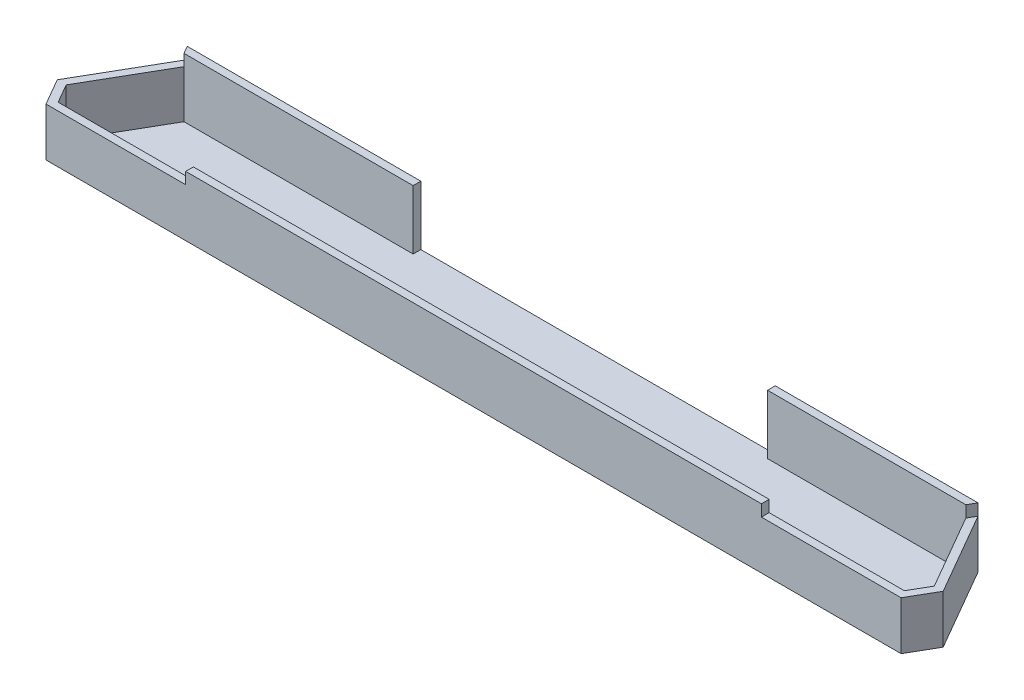
SolidWorks part; units mm, degrees
note: The reader was unsure of these and kept them because the rebuilt part matched: shared geometry of "Sketch1<3>", "Sketch1<4>".
ref_plane "Front Plane" through (0, 0, 0) normal (0, 0, 1) x (1, 0, 0)
ref_plane "Top Plane" through (0, 0, 0) normal (0, 1, 0) x (1, 0, 0)
ref_plane "Right Plane" through (0, 0, 0) normal (1, 0, 0) x (0, 0, -1)
sketch "Sketch1" plane through (0, 0, 0) normal (0, 1, 0) x (1, 0, 0)
  line L7 (-115, 0) -> (-111, -6.9282)
  line L9 (115, 0) -> (111, -6.9282)
  line L17 (-102.6494, 21.3918) -> (-101.4947, 19.3918)
  line L24 (102.6494, 21.3918) -> (101.4947, 19.3918)
  line L25 (-115, 0) -> (115, 0) construction
  line L26 (-115, 0) -> (-102.6494, 21.3918)
  line L27 (-113, -3.4641) -> (-107, 0) construction
  line L28 (0, -6.9282) -> (0, 21.3918) construction
  line L29 (113, -3.4641) -> (107, 0) construction
  line L30 (0, 21.3918) -> (-42.01, 21.3918) construction
  line L31 (-42.01, 21.3918) -> (-42.01, 19.3918)
  line L33 (-112.6906, 0) -> (-109.8453, -4.9282)
  line L36 (112.6906, 0) -> (109.8453, -4.9282)
  line L46 (-74.74, -4.9282) -> (74.74, -4.9282)
  line L49 (74.74, -6.9282) -> (-74.74, -6.9282)
  line L50 (-112.6906, 0) -> (-101.4947, 19.3918)
  line L51 (-102.6494, 21.3918) -> (-42.01, 21.3918)
  line L52 (-101.4947, 19.3918) -> (-42.01, 19.3918)
  line L53 (-42.01, 21.3918) -> (50.01, 21.3918) construction
  line L54 (50.01, 21.3918) -> (102.6494, 21.3918)
  line L55 (-109.8453, -4.9282) -> (-74.74, -4.9282)
  line L56 (109.8453, -4.9282) -> (74.74, -4.9282)
  line L57 (-111, -6.9282) -> (-74.74, -6.9282)
  line L59 (101.4947, 19.3918) -> (50.01, 19.3918)
  line L60 (102.6494, 21.3918) -> (115, 0)
  line L61 (50.01, 19.3918) -> (50.01, 21.3918)
  line L62 (101.4947, 19.3918) -> (112.6906, 0)
  line L64 (-42.01, 21.3918) -> (50.01, 21.3918)
  line L68 (0, -6.9282) -> (-74.74, -6.9282) construction
  line L69 (-74.74, -6.9282) -> (-74.74, -4.9282)
  line L77 (111, -6.9282) -> (74.74, -6.9282)
  line L78 (74.74, -6.9282) -> (74.74, -4.9282)
  line L79 (0, -4.9282) -> (0, 19.3918) construction
  line L81 (0, 19.3918) -> (0, 21.3918) construction
  point P56 (0, 19.3918)
  point P60 (0, 21.3918)
  dimension "D1" = 8
  dimension "D2" = 42.01
  dimension "D3" = 8
  dimension "D4" = 230
  dimension "D5" = 92.02
  dimension "D7" = 74.74
extrude "Boss-Extrude1" add sketch "Sketch1" along normal blind 0.2
extrude "Boss-Extrude2" add sketch "Sketch1<3>" along normal blind 12.58
sketch "Sketch1<3>" plane through (0, 0, 0) normal (0, 1, 0) x (1, 0, 0) same geometry as "Sketch1"
extrude "Boss-Extrude3" add sketch "Sketch1<4>" along normal blind 15.58
sketch "Sketch1<4>" plane through (0, 0, 0) normal (0, 1, 0) x (1, 0, 0) same geometry as "Sketch1"
